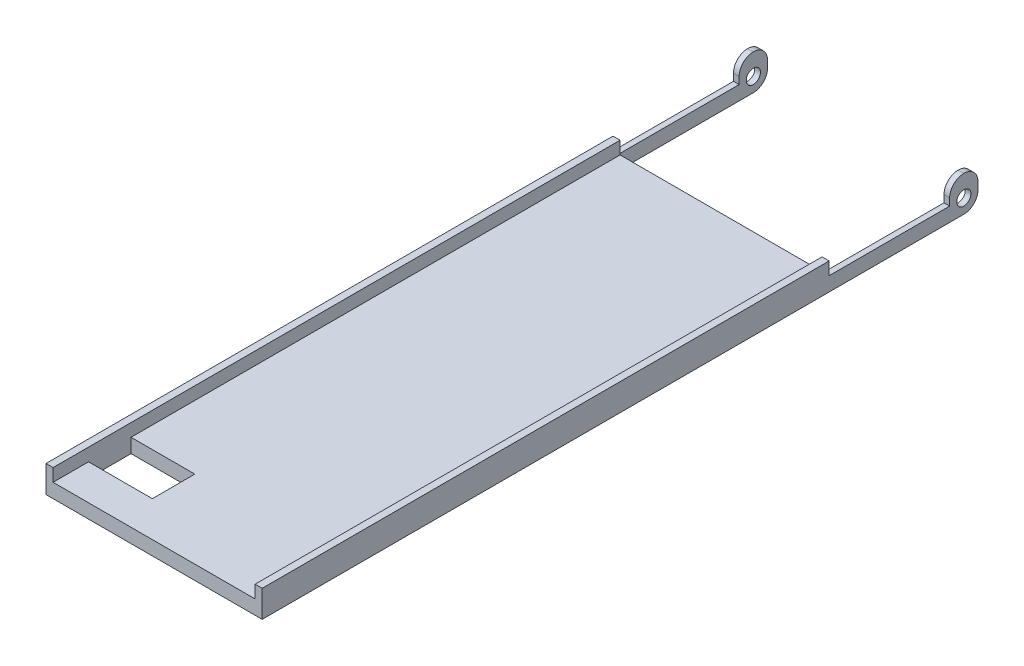
SolidWorks part; units mm, degrees
ref_plane "Front Plane" through (0, 0, 0) normal (0, 0, 1) x (1, 0, 0)
ref_plane "Top Plane" through (0, 0, 0) normal (0, 1, 0) x (1, 0, 0)
ref_plane "Right Plane" through (0, 0, 0) normal (1, 0, 0) x (0, 0, -1)
sketch "Sketch1" plane through (0, 0, 0) normal (0, 1, 0) x (1, 0, 0)
  line L1 (-15.25, -42.5) -> (15.25, -42.5)
  line L2 (-15.25, -42.5) -> (-15.25, 42.5)
  line L3 (-15.25, 42.5) -> (15.25, 42.5)
  line L4 (15.25, -42.5) -> (15.25, 42.5)
  line L5 (-15.25, -42.5) -> (15.25, 42.5) construction
  line L6 (-15.25, 42.5) -> (15.25, -42.5) construction
  point P0 (0, 0)
  dimension "D1" = 85
  dimension "D2" = 30.5
extrude "Boss-Extrude1" add sketch "Sketch1" along normal blind 2 contours L4 L3 L2 L1
sketch "Sketch2" plane through (0, 2, 0) normal (0, 1, 0) x (1, 0, 0)
  line L0 (0, 24.5) -> (0, -42.5) construction
  line L2 (-15.25, -42.5) -> (15.25, -42.5) construction
  line L3 (-15.25, -42.5) -> (-15.25, 42.5) construction
  line L4 (14.45, 42.5) -> (-14.45, 42.5)
  line L7 (-14.45, 42.5) -> (-14.45, 24.5)
  line L8 (14.45, 42.5) -> (14.45, 24.5)
  line L10 (-14.45, 24.5) -> (-14.45, 22.5)
  line L11 (-14.45, 22.5) -> (14.45, 22.5)
  line L12 (14.45, 24.5) -> (14.45, 22.5)
  dimension "D1" = 0.8
  dimension "D2" = 18
  dimension "D3" = 2
extrude "Cut-Extrude1" cut sketch "Sketch2" against normal up to vertex (2 mm away) up to point (15.25, 0, -42.5)
sketch "Sketch5" plane through (0, 2, 0) normal (0, 1, 0) x (1, 0, 0)
  line L0 (-15.25, -42.5) -> (-15.25, 42.5) construction
  line L1 (-14.45, 42.5) -> (-15.25, 42.5)
  line L2 (-14.45, 42.5) -> (-14.45, 38.5)
  line L3 (-14.45, 38.5) -> (-15.25, 38.5)
  line L4 (-15.25, 42.5) -> (-15.25, 38.5)
  dimension "D1" = 4
extrude "Boss-Extrude2" add sketch "Sketch5" along normal blind 3 contours L2 L3 L4 L1
sketch "Sketch6" plane through (-15.25, 0, 0) normal (-1, 0, 0) x (0, 0, 1)
  line L0 (42.5, 0) -> (-42.5, 0) construction
  line L1 (-42.5, 5) -> (-42.5, 0) construction
  circle A0 centre (-40.5, 2) radius 1
  dimension "D1" = 2
  dimension "D2" = 2
  dimension "D3" = 2
extrude "Cut-Extrude2" cut sketch "Sketch6" against normal up to vertex (0.8 mm away) contours A0 up to point (-14.45, 5, -42.5)
ref_plane "Plane1" through (0, 0, 0) normal (1, 0, 0) x (0, 0, -1)
mirror "Mirror1" about plane through (0, 0, 0) normal (1, 0, 0) of "Cut-Extrude2", "Boss-Extrude2"
fillet "Fillet1" radius 2 3 edges at (-14.85, 0, -42.5) (-14.85, 5, -42.5) (-14.85, 5, -38.5)
fillet "Fillet2" radius 2 3 edges at (14.85, 0, -42.5) (14.85, 5, -38.5) (14.85, 5, -42.5)
sketch "Sketch7" plane through (0, 0, 42.5) normal (0, 0, 1) x (1, 0, 0)
  line L1 (-15.25, 2) -> (15.25, 2)
  line L2 (-15.25, 2) -> (-15.25, 0)
  line L3 (-15.25, 0) -> (15.25, 0)
  line L4 (15.25, 2) -> (15.25, 0)
extrude "Boss-Extrude3" add sketch "Sketch7" along normal blind 16
sketch "Sketch8" plane through (0, 2, 0) normal (0, 1, 0) x (1, 0, 0)
  line L0 (-15.25, -58.5) -> (-15.25, 38.5) construction
  line L1 (15.25, -58.5) -> (-15.25, -58.5)
  line L2 (15.25, -58.5) -> (15.25, 21.5)
  line L3 (15.25, 21.5) -> (-15.25, 21.5)
  line L4 (-15.25, -58.5) -> (-15.25, 21.5)
  line L5 (-14.45, 22.5) -> (14.45, 22.5) construction
  dimension "D1" = 1
extrude "Boss-Extrude4" add sketch "Sketch8" along normal blind 1.8
sketch "Sketch9" plane through (0, 3.8, 0) normal (0, 1, 0) x (1, 0, 0)
  line L0 (15.25, 21.5) -> (-15.25, 21.5) construction
  line L1 (-14.25, 21.5) -> (14.25, 21.5)
  line L2 (-14.25, 21.5) -> (-14.25, -58.5)
  line L3 (-14.25, -58.5) -> (14.25, -58.5)
  line L4 (14.25, 21.5) -> (14.25, -58.5)
  line L5 (-15.25, -58.5) -> (15.25, -58.5) construction
  line L6 (-15.25, 21.5) -> (-15.25, -58.5) construction
  line L7 (15.25, -58.5) -> (15.25, 21.5) construction
  dimension "D1" = 1
  dimension "D2" = 1
extrude "Cut-Extrude3" cut sketch "Sketch9" against normal up to vertex (1.8 mm away) up to point (-14.45, 2, -22.5)
sketch "Sketch10" plane through (0, 0, -22.5) normal (0, 0, -1) x (-1, 0, 0)
  line L1 (-14.45, 2) -> (14.45, 2)
  line L2 (-14.45, 2) -> (-14.45, 0)
  line L3 (-14.45, 0) -> (14.45, 0)
  line L4 (14.45, 2) -> (14.45, 0)
extrude "Cut-Extrude4" cut sketch "Sketch10" against normal up to vertex (1 mm away) up to point (15.25, 2, -21.5)
sketch "Sketch11" plane through (0, 2, 0) normal (0, 1, 0) x (1, 0, 0)
  line L0 (-14.25, 21.5) -> (-14.25, -58.5) construction
  line L1 (-14.25, -53.5) -> (-5.25, -53.5)
  line L2 (-14.25, -53.5) -> (-14.25, -47.5)
  line L3 (-14.25, -47.5) -> (-5.25, -47.5)
  line L4 (-5.25, -53.5) -> (-5.25, -47.5)
  line L5 (-14.25, -58.5) -> (14.25, -58.5) construction
  dimension "D1" = 9
  dimension "D2" = 6
  dimension "D3" = 5
extrude "Cut-Extrude5" cut sketch "Sketch11" against normal up to vertex (2 mm away) up to point (-15.25, 0, 58.5)
